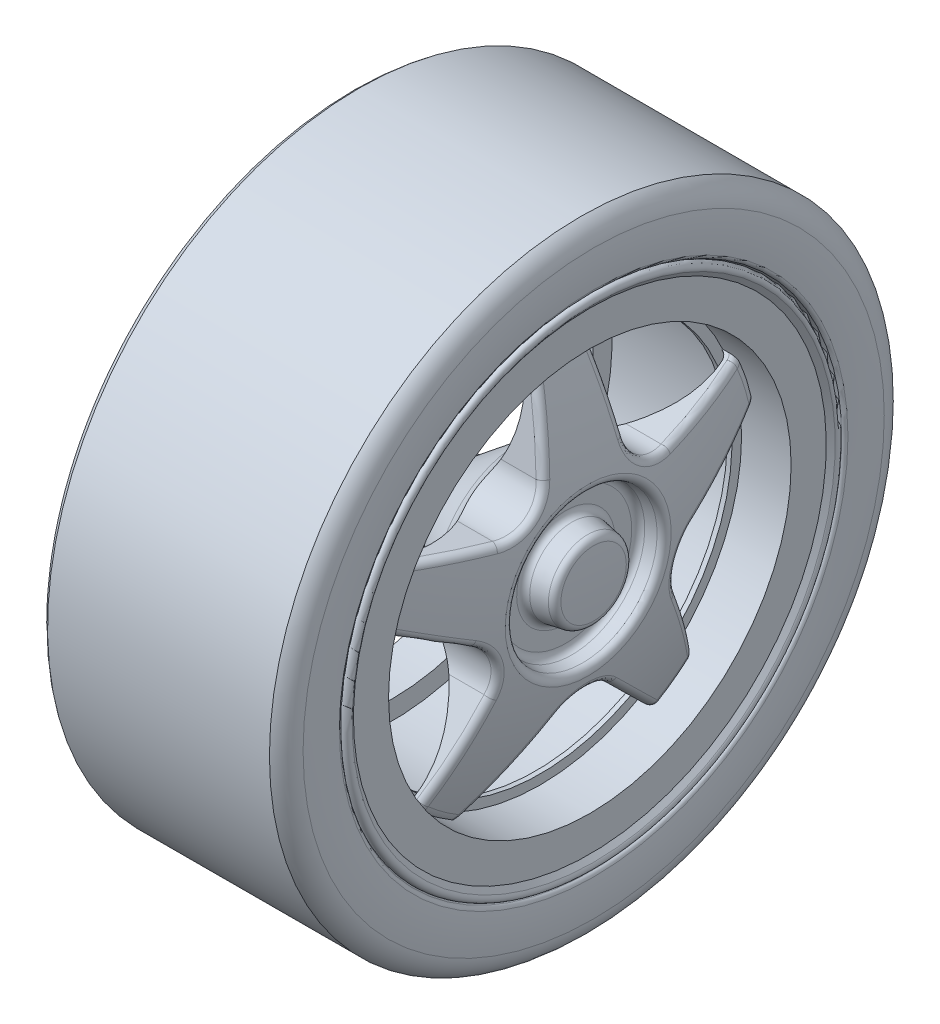
SolidWorks part; units mm, degrees
material "ABS"
ref_plane "Alzado" through (0, 0, 0) normal (0, 0, 1) x (1, 0, 0)
ref_plane "Planta" through (0, 0, 0) normal (0, 1, 0) x (1, 0, 0)
ref_plane "Vista lateral" through (0, 0, 0) normal (1, 0, 0) x (0, 0, -1)
sketch "Croquis1" plane through (0, 0, 0) normal (0, 0, 1) x (1, 0, 0)
  line L0 (-13, 26) -> (13, 26) construction
  line L1 (-13, 0) -> (13, 0) construction
  line L2 (-13, 0) -> (-13, 33) construction
  line L3 (-13, 33) -> (13, 33) construction
  line L4 (13, 0) -> (13, 33) construction
  line L5 (-12.2647, 25.9412) -> (-10.5, 25)
  line L6 (12.2647, 25.9412) -> (10.5, 25)
  line L7 (-10.5, 25) -> (10.5, 25)
  line L8 (0, 26) -> (0, 25) construction
  line L9 (12.8997, 25.1996) -> (12.5, 24.6678)
  line L10 (12.5, 24.6678) -> (12.5, 21)
  line L11 (12.5, 21) -> (8.8322, 21)
  line L12 (12.8574, 4) -> (10, 4.5)
  line L13 (10, 4.5) -> (10, 7.5)
  line L14 (10, 7.5) -> (12.4379, 7.9266)
  line L15 (-12.8997, 25.1996) -> (-12.5, 24.6678)
  line L16 (-12.5, 24.6678) -> (-12.5, 21)
  line L17 (-12.5, 21) -> (6.8322, 21)
  line L18 (13, 0) -> (-16, 0)
  line L19 (-16, 0) -> (-16, 4)
  line L20 (-16, 4) -> (0.8553, 6.9494)
  line L21 (13, 0) -> (15.4749, 0) construction
  line L22 (10, 6) -> (12.4749, 6) construction
  line L23 (-0.8188, 16.5163) -> (8.2297, 20.045) construction
  line L24 (6.8322, 21) -> (8.8322, 21)
  arc A0 (-12.8997, 25.1996) -> (-12.2647, 25.9412) centre (-12.5, 25.5) cw
  arc A1 (12.8997, 25.1996) -> (12.2647, 25.9412) centre (12.5, 25.5) ccw
  arc A2 (8.8322, 21) -> (9.1614, 20.4083) centre (6.8322, 19.5) cw
  arc A3 (9.1614, 20.4083) -> (12.4379, 7.9266) centre (-43.1704, 0) cw
  arc A4 (12.4379, 7.9266) -> (12.8574, 4) centre (-43.1704, 0) cw construction
  arc A5 (12.8574, 4) -> (13, 0) centre (-43.1704, 0) cw
  arc A6 (0.8553, 6.9494) -> (8.2297, 20.045) centre (-0.8188, 16.5163) ccw
  arc A7 (8.2297, 20.045) -> (6.8322, 21) centre (6.8322, 19.5) ccw
  dimension "D6" = 0.5
  dimension "D9" = 2.5
  dimension "D15" = 1
  dimension "D1" = 33
  dimension "D2" = 26
  dimension "D3" = 26
  dimension "D4" = 1
  dimension "D5" = 2
  dimension "D7" = 25
  dimension "D8" = 5
  dimension "D10" = 8
  dimension "D11" = 3
  dimension "D12" = 0.5
  dimension "D13" = 3
  dimension "D14" = 29
revolve "Revolución1" add sketch "Croquis1" angle 360 about L18 region at (0, 23.0694, 0)
revolve "Revolución2" add sketch "Croquis1<3>" angle 360 about L18 region at (1.3597, 4.9037, 0)
sketch "Croquis1<3>" plane through (0, 0, 0) normal (0, 0, 1) x (1, 0, 0) same geometry as "Croquis1"
sketch "Croquis2" plane through (0, 0, 0) normal (1, 0, 0) x (0, 0, -1)
  line L0 (-19.0325, 8.8749) -> (-8.789, 7.3126)
  line L1 (-2.4669, 21.4052) -> (-2.5592, 20.8435) construction
  line L2 (-19.5952, 8.9608) -> (-19.0325, 8.8749) construction
  line L3 (-2.5592, 20.8435) -> (-4.2387, 10.6185)
  circle A0 centre (0, 21) radius 2.5 construction
  circle A1 centre (0, 0) radius 21 construction
  circle A2 centre (19.9722, 6.4894) radius 2.5
  circle A3 centre (12.3435, -16.9894) radius 2.5
  circle A4 centre (-12.3435, -16.9894) radius 2.5
  circle A5 centre (-19.9722, 6.4894) radius 2.5 construction
  arc A6 (-8.789, 7.3126) -> (-4.2387, 10.6185) centre (-8.1858, 11.2669) ccw
  arc A7 (-4.2387, 10.6185) -> (-8.789, 7.3126) centre (-8.1858, 11.2669) ccw construction
  circle A8 centre (0, 0) radius 9.9266 construction
  circle A9 centre (0, 0) radius 7.9266 construction
  arc A10 (-19.0325, 8.8749) -> (-2.5592, 20.8435) centre (0, 0) cw
  point P16 (0, 0)
  dimension "D1" = 5
  dimension "D3" = 8
  dimension "D4" = 2
  dimension "D2" = 5
extrude "Cortar-Extruir1" cut sketch "Croquis2" along normal blind 29 contours A10 L0 A6 L3 region at (0, 13.2098, 9.5975)
ref_axis "Eje1" through (0.8553, 0, 0) along (-1, 0, 0)
pattern_circular "MatrizC1" count 5 over 360 about axis through (0.8553, 0, 0) along (-1, 0, 0) of "Cortar-Extruir1"
sketch "Croquis3" plane through (0, 0, 0) normal (0, 0, 1) x (1, 0, 0)
  line L0 (7.3322, 22.5) -> (7.3322, 19.5)
  line L1 (6.8322, 21) -> (-8.1678, 21)
  line L2 (6.8322, 21) -> (6.8322, 23)
  line L3 (6.8322, 23) -> (-8.1678, 23)
  line L4 (-8.1678, 21) -> (-8.1678, 23)
  line L5 (7.3322, 19.5) -> (6.8322, 19.5)
  line L6 (6.8322, 19.5) -> (6.8322, 21)
  line L7 (6.8322, 23) -> (7.3322, 23)
  line L8 (7.3322, 23) -> (7.3322, 22.5)
  arc A0 (6.8322, 23) -> (7.3322, 22.5) centre (6.8322, 22.5) cw construction
  dimension "D1" = 2
  dimension "D2" = 0.5
  dimension "D3" = 1.5
  dimension "D4" = 15
revolve "Cortar-Revolución1" cut sketch "Croquis3" angle 360 about axis through (0.8553, 0, 0) along (-1, 0, 0) region at (7.0822, 21.25, 0) region at (-0.6678, 22, 0)
sketch "Croquis4" plane through (0, 0, 0) normal (0, 0, 1) x (1, 0, 0)
  line L0 (12.5, 21) -> (7.3322, 21) construction
  line L1 (7.3322, 23) -> (6.8322, 23)
  line L2 (7.3322, 23) -> (7.3322, 20)
  line L3 (7.3322, 20) -> (6.8322, 20)
  line L4 (6.8322, 23) -> (6.8322, 21.5) construction
  line L5 (6.8322, 23) -> (5.3322, 23)
  line L6 (7.3322, 23) -> (-8.1678, 23) construction
  line L7 (6.8322, 21.5) -> (6.8322, 20)
  arc A0 (5.3322, 23) -> (6.8322, 21.5) centre (5.3322, 21.5) cw
  dimension "D1" = 1
  dimension "D2" = 0.5
revolve "Revolución3" add sketch "Croquis4" angle 360 about axis through (0.8553, 0, 0) along (-1, 0, 0)
fillet "Redondeo1" radius 0.75 28 edges at (12.1094, -3.5064, 9.3252) (10.7135, 1.5145, 15.7908) (10.7135, 8.0563, 13.6652) (12.1094, 7.7853, 6.2165) (10.7135, 15.4859, 3.4392) (10.7135, 15.4859, -3.4392) (12.1094, 8.318, -5.4832) (10.7135, 8.0563, -13.6652) (10.7135, 1.5145, -15.7908) (12.1094, -2.6445, -9.6053) (10.7135, -10.5069, -11.8848) (10.7135, -14.5499, -6.32) (12.1094, -9.9523, -0.4532) (10.7135, -14.5499, 6.32) (10.7135, -10.5069, 11.8848) (12.8574, 4, 0) (10, 4.5, 0) (10, 7.5, 0)
sketch "Croquis6" plane through (0, 0, 0) normal (0, 0, 1) x (1, 0, 0)
  line L0 (-16, 4) -> (-1, 4)
  line L1 (-1, 4) -> (5.1987, 8.8928)
  line L2 (-16, 4) -> (0.8553, 6.9494)
  arc A0 (0.8553, 6.9494) -> (5.1987, 8.8928) centre (-0.8188, 16.5163) ccw
  arc A1 (0.8553, 6.9494) -> (8.8934, 16.5163) centre (-0.8188, 16.5163) ccw construction
  dimension "D1" = 15
revolve "Cortar-Revolución4" cut sketch "Croquis6" angle 360 about axis through (0.8553, 0, 0) along (-1, 0, 0)
sketch "Croquis7" plane through (0, 0, 0) normal (0, 0, 1) x (1, 0, 0)
  line L0 (-13, 0) -> (-13, 33) construction
  line L1 (-12.2647, 25.9412) -> (-10.5, 25) construction
  line L2 (12.6381, 26.1403) -> (10.5, 25)
  line L3 (-10.5, 25) -> (10.5, 25)
  line L4 (13, 0) -> (13, 33) construction
  line L5 (0, 32.9) -> (0, 33) construction
  line L8 (-13, 33) -> (13, 33) construction
  line L9 (-12.6381, 26.1403) -> (-10.5, 25)
  arc A0 (-12.9, 26.5288) -> (-12.9, 30.316) centre (4.9782, 28.4224) cw
  arc A1 (-12.2647, 25.9412) -> (-12.8997, 25.1996) centre (-12.5, 25.5) ccw construction
  arc A2 (-9.8562, 32.9994) -> (9.8562, 32.9994) centre (0, 521.6534) ccw
  arc A3 (12.9, 30.316) -> (12.9, 26.5288) centre (-4.9782, 28.4224) cw
  arc A4 (12.9, 30.316) -> (9.8562, 32.9994) centre (9.9167, 30) ccw
  arc A5 (-12.9, 30.316) -> (-9.8562, 32.9994) centre (-9.9167, 30) cw
  arc A6 (-12.9, 26.5288) -> (-12.6381, 26.1403) centre (-12.4028, 26.5815) ccw
  arc A7 (12.9, 26.5288) -> (12.6381, 26.1403) centre (12.4028, 26.5815) cw
  arc A8 (12.8997, 25.1996) -> (12.2647, 25.9412) centre (12.5, 25.5) ccw construction
  dimension "D1" = 3
  dimension "D2" = 0.1
  dimension "D3" = 0.1
revolve "Revolución4" add sketch "Croquis7" angle 360 about L18
fillet "Redondeo2" radius 0.75 1 edges at (12.4379, 7.9266, 0)
sketch "Croquis8" plane through (-16, 0, 0) normal (-1, 0, 0) x (0, 0, 1)
  line L0 (-1.8, 2.0125) -> (-1.8, -2.0125)
  line L1 (1.8, -2.0125) -> (1.8, 2.0125)
  circle A0 centre (0, 0) radius 2.7 construction
  circle A1 centre (0, 0) radius 4 construction
  arc A2 (-1.8, 2.0125) -> (1.8, 2.0125) centre (0, 0) cw
  arc A3 (-1.8, -2.0125) -> (1.8, -2.0125) centre (0, 0) ccw
  dimension "D1" = 5.4
  dimension "D2" = 3.6
extrude "Cortar-Extruir2" cut sketch "Croquis8" against normal blind 10
sketch "Эскиз1" plane through (0, 0, 0) normal (1, 0, 0) x (0, 0, -1)
  circle A0 centre (0, 0) radius 32.5
  circle A1 centre (0, 0) radius 41.1363
extrude "Вырез-Вытянуть4" cut sketch "Эскиз1" along normal through all both and the other way through all contours A1 A0 region at (0, 0, 39.9728)
sketch3d "3DSketch1"
  line L0 (0, 0, 0) -> (-10, 0, 0) construction
  line L1 (0, 0, 0) -> (0, 10, 0) construction
  line L2 (0, 0, 0) -> (0, 0, -10) construction
